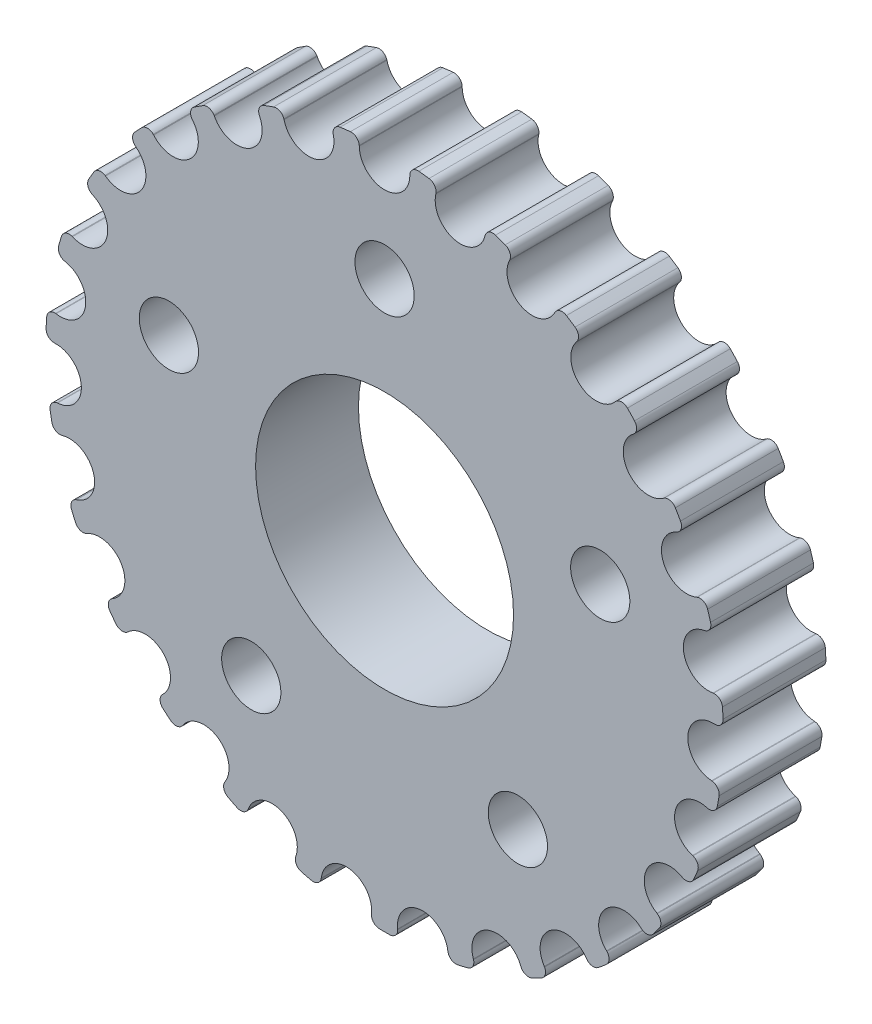
SolidWorks part; units mm, degrees
ref_plane "Front Plane" through (0, 0, 0) normal (0, 0, 1) x (1, 0, 0)
ref_plane "Top Plane" through (0, 0, 0) normal (0, 1, 0) x (1, 0, 0)
ref_plane "Right Plane" through (0, 0, 0) normal (1, 0, 0) x (0, 0, -1)
sketch "Pitch diameter" plane through (0, 0, 0) normal (0, 0, 1) x (1, 0, 0)
  circle A0 centre (0, 0) radius 21.4859 construction
  dimension "D1" = 42.9718
sketch "Sketch2" plane through (0, 0, 0) normal (0, 0, 1) x (1, 0, 0)
  circle A0 centre (0, 0) radius 20.9144
  dimension "D1" = 41.8288
extrude "Boss-Extrude1" add sketch "Sketch2" along normal blind 6.35
sketch "Sketch3" plane through (0, 0, 0) normal (0, 0, -1) x (-1, 0, 0)
  line L0 (-1.6014, 20.853) -> (-1.56, 20.3144)
  line L1 (1.6014, 20.853) -> (1.56, 20.3144)
  line L2 (-1.56, 20.3144) -> (1.56, 20.3144) construction
  circle A0 centre (0, 0) radius 20.9144 construction
  arc A1 (-1.56, 20.3144) -> (1.56, 20.3144) centre (0, 20.3144) ccw
  circle A2 centre (0, 0) radius 20.9144 construction
  arc A3 (1.6014, 20.853) -> (-1.6014, 20.853) centre (0, 0) ccw
  point P10 (0, 20.3144)
  point P15 (0, 18.7544)
  point P16 (0, 20.9144)
  dimension "D1" = 1.56
  dimension "D2" = 2.16
extrude "Cut-Extrude1" cut sketch "Sketch3" against normal through all
fillet "Fillet1" radius 0.5 2 edges at (-1.6014, 20.853, 3.175) (1.6014, 20.853, 3.175)
pattern_circular "CirPattern1" count 27 over 360 about axis through (0, 0, 0) along (0, 0, 1) of "Cut-Extrude1", "Fillet1"
sketch "Sketch4" plane through (0, 0, 6.35) normal (0, 0, 1) x (1, 0, 0)
  circle A0 centre (0, 0) radius 7.9629
  dimension "D1" = 15.9258
extrude "Cut-Extrude2" cut sketch "Sketch4" against normal through all
sketch "Sketch5" plane through (0, 0, 6.35) normal (0, 0, 1) x (1, 0, 0)
  line L0 (0, 0) -> (0, 14)
  point P0 (0, 0)
  point P7 (0, 0)
  dimension "D1" = 14
sketch "Sketch9" plane through (0, 0, 6.35) normal (0, 0, 1) x (1, 0, 0)
  point P0 (0, 14)
hole_wizard "#6 Clearance Hole1" positions "Sketch9" profile "Sketch10" hole size "#6" standard "ANSI Inch" end condition through all
sketch "Sketch10" plane through (0, 14, 6.35) normal (1, 0, 0) x (0, -1, 0)
  line L0 (0, 0) -> (0, 6.35)
  line L1 (0, 6.35) -> (1.8288, 6.35)
  line L2 (1.8288, 6.35) -> (1.8288, 0)
  line L5 (1.8288, 0) -> (0, 0)
  line L11 (0, -6.35) -> (0, 107.95) construction
  dimension "Thru Hole Dia." = 3.6576
  dimension "Thru Hole Depth" = 6.35
pattern_circular "CirPattern2" count 5 over 360 about axis through (0, 0, 6.35) along (0, 0, 1) of "#6 Clearance Hole1"
equation "\"NumberOfTeeth\"= 27"
equation "\"Pitch\"= 5mm"
equation "\"PitchDiameter\"= ( \"Pitch\" * \"NumberOfTeeth\" ) / Pi"
equation "\"OD\"= \"PitchDiameter\" - 0.0225in * 2"
equation "\"D1@Pitch diameter\" = \"PitchDiameter\""
equation "\"D1@Sketch2\"=\"OD\""
equation "\"D1@CirPattern1\"=\"NumberOfTeeth\""
